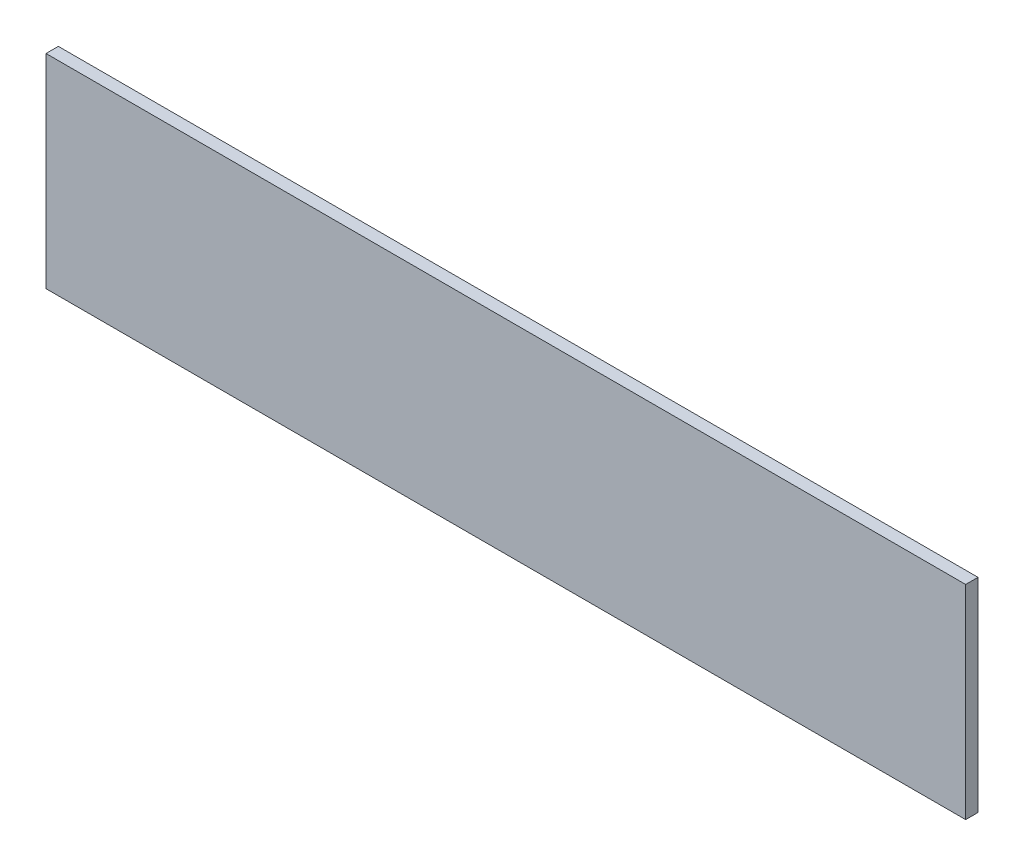
SolidWorks part; units mm, degrees
ref_plane "Front Plane" through (0, 0, 0) normal (0, 0, 1) x (1, 0, 0)
ref_plane "Top Plane" through (0, 0, 0) normal (0, 1, 0) x (1, 0, 0)
ref_plane "Right Plane" through (0, 0, 0) normal (1, 0, 0) x (0, 0, -1)
sketch "Sketch1" plane through (0, 0, 0) normal (0, 0, 1) x (1, 0, 0)
  line L1 (-74.5, -16.5) -> (74.5, -16.5)
  line L2 (-74.5, -16.5) -> (-74.5, 16.5)
  line L3 (-74.5, 16.5) -> (74.5, 16.5)
  line L4 (74.5, -16.5) -> (74.5, 16.5)
  line L5 (-74.5, -16.5) -> (74.5, 16.5) construction
  line L6 (-74.5, 16.5) -> (74.5, -16.5) construction
  point P0 (0, 0)
  dimension "D1" = 149
  dimension "D2" = 33
extrude "Boss-Extrude1" add sketch "Sketch1" along normal blind 2
